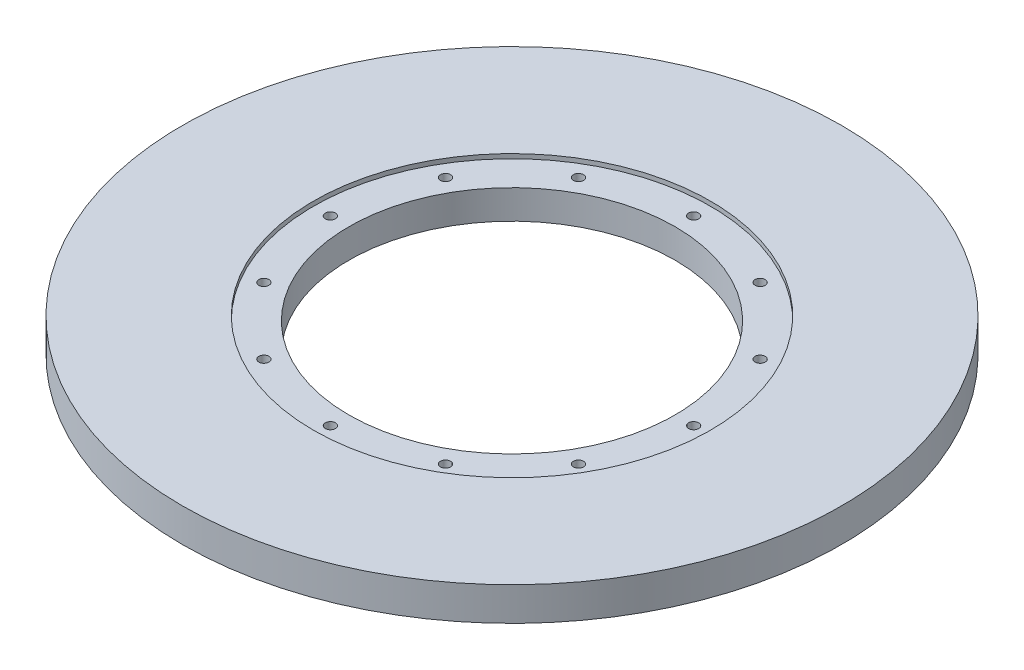
SolidWorks part; units mm, degrees
material "6061-T6 (SS)"
ref_plane "Front Plane" through (0, 0, 0) normal (0, 0, 1) x (1, 0, 0)
ref_plane "Top Plane" through (0, 0, 0) normal (0, 1, 0) x (1, 0, 0)
ref_plane "Right Plane" through (0, 0, 0) normal (1, 0, 0) x (0, 0, -1)
sketch "Sketch1" plane through (0, 0, 0) normal (0, 1, 0) x (1, 0, 0)
  line L5 (0, 0) -> (127.635, 0)
  line L6 (0, 0) -> (0, 127.635)
  line L7 (0, 127.635) -> (127.635, 127.635)
  line L8 (127.635, 0) -> (127.635, 127.635)
  dimension "D1" = 127.635
  dimension "D2" = 127.635
extrude "Boss-Extrude1" add sketch "Sketch1" along normal blind 9.525 contours L5 L8 L7 L6
sketch "Sketch13" plane through (0, 9.525, 0) normal (0, 1, 0) x (1, 0, 0)
  circle A0 centre (63.8175, 63.8175) radius 93.6625
  dimension "D1" = 187.325
extrude "Boss-Extrude2" add sketch "Sketch13" against normal up to surface (9.525 mm away) contours A0 up to face at (63.8175, 0, -63.8175)
sketch "Sketch6" plane through (127.635, 0, 0) normal (1, 0, 0) x (0, 0, -1)
  circle A0 centre (4.7625, 4.7625) radius 1.3526
  dimension "D1" = 2.7051
extrude "6-32 hole1" cut sketch "Sketch6" against normal blind 12.7
sketch "Sketch7" [suppressed] plane through (0, 0, -127.635) normal (0, 0, -1) x (-1, 0, 0)
  circle A0 centre (-122.8725, 4.7625) radius 1.3525
  dimension "D1" = 2.7051
sketch "Sketch8" [suppressed] plane through (0, 0, 0) normal (-1, 0, 0) x (0, 0, 1)
  circle A0 centre (-122.8725, 4.7625) radius 1.3525
  dimension "D1" = 2.7051
sketch "Sketch9" [suppressed] plane through (0, 0, 0) normal (0, 0, 1) x (1, 0, 0)
  circle A0 centre (4.7625, 4.7625) radius 1.3526
  dimension "D1" = 2.7051
sketch "Sketch5" plane through (0, 9.525, 0) normal (0, 1, 0) x (1, 0, 0)
  circle A0 centre (63.8175, 63.8175) radius 46.355
  circle A1 centre (63.8175, 63.8175) radius 93.6625 construction
  point P8 (0, 0)
  dimension "D1" = 92.71
extrude "Cut-Extrude1" cut sketch "Sketch5" against normal blind 9.525
sketch "Sketch11" plane through (0, 9.525, 0) normal (0, 1, 0) x (1, 0, 0)
  line L0 (63.8175, 63.8175) -> (63.8175, 115.443) construction
  circle A0 centre (63.8175, 115.443) radius 1.4351
  dimension "D2" = 2.8702
  dimension "D1" = 51.6255
extrude "Cut-Extrude3" cut sketch "Sketch11" against normal through all contours A0
pattern_circular "CirPattern1" count 12 over 360 about axis through (63.8175, 9.525, -63.8175) along (0, 1, 0) of "Cut-Extrude3"
sketch "Sketch12" plane through (0, 9.525, 0) normal (0, 1, 0) x (1, 0, 0)
  circle A0 centre (63.8175, 63.8175) radius 56.4198
  dimension "D1" = 112.8395
extrude "Cut-Extrude4" cut sketch "Sketch12" against normal blind 1.27
